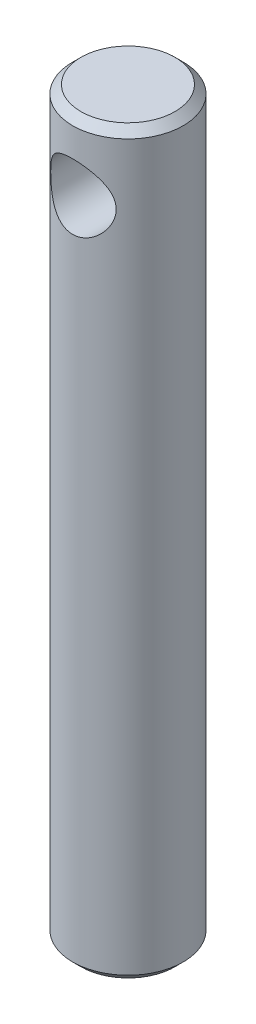
SolidWorks part; units mm, degrees
material "Plain Carbon Steel"
ref_plane "Front" through (0, 0, 0) normal (0, 0, 1) x (1, 0, 0)
ref_plane "Top" through (0, 0, 0) normal (0, 1, 0) x (1, 0, 0)
ref_plane "Right" through (0, 0, 0) normal (1, 0, 0) x (0, 0, -1)
sketch "Sketch1" plane through (0, 0, 0) normal (0, 1, 0) x (1, 0, 0)
  circle A0 centre (0, 0) radius 13.5
  dimension "D1" = 27
extrude "Boss-Extrude1" add sketch "Sketch1" along normal blind 181
sketch "Sketch2" plane through (0, 0, 0) normal (0, 0, 1) x (1, 0, 0)
  line L0 (13.5, 181) -> (-13.5, 181) construction
  circle A0 centre (0, 164) radius 8
  dimension "D1" = 16
  dimension "D2" = 17
extrude "Cut-Extrude1" cut sketch "Sketch2" against normal through all both and the other way through all
chamfer "Chamfer1" distance 2 angle 45 2 edges at (0, 181, 13.5) (0, 0, 13.5)
ref_point "Point1"
ref_axis "Axis1" through (0, 164, -13.5) along (0, 0, 1)
